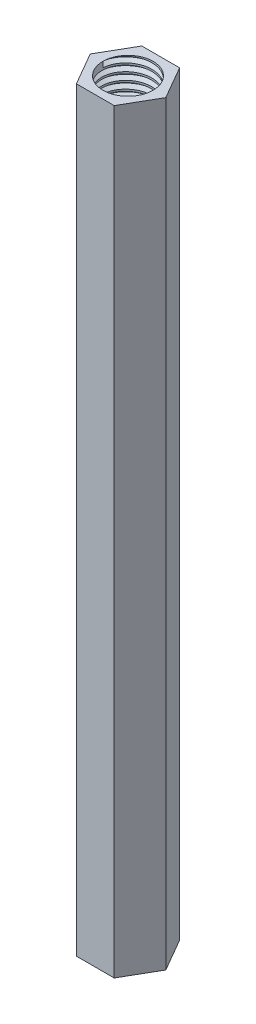
SolidWorks part; units mm, degrees
ref_plane "Front Plane" through (0, 0, 0) normal (0, 0, 1) x (1, 0, 0)
ref_plane "Top Plane" through (0, 0, 0) normal (0, 1, 0) x (1, 0, 0)
ref_plane "Right Plane" through (0, 0, 0) normal (1, 0, 0) x (0, 0, -1)
sketch "Sketch1" plane through (0, 0, 0) normal (0, 1, 0) x (1, 0, 0)
  line L1 (2.5, 0) -> (1.25, 2.1651)
  line L2 (1.25, 2.1651) -> (-1.25, 2.1651)
  line L3 (-1.25, 2.1651) -> (-2.5, 0)
  line L4 (-2.5, 0) -> (-1.25, -2.1651)
  line L5 (-1.25, -2.1651) -> (1.25, -2.1651)
  line L6 (1.25, -2.1651) -> (2.5, 0)
  circle A0 centre (0, 0) radius 2.1651 construction
  dimension "D1" = 2.5
extrude "Boss-Extrude1" add sketch "Sketch1" along normal blind 50
sketch "Sketch2" plane through (0, 50, 0) normal (0, 1, 0) x (1, 0, 0)
  circle A0 centre (0, 0) radius 1.6604
extrude "Cut-Extrude1" cut sketch "Sketch2" against normal through all
thread "Thread1" pitch 0.5 method cut profile "Thread Profile1" start angle 0, offset 0, length 10, pitch 0.5, diameter 3.3208
ref_plane "Plane1" through (1.6604, 0, 0) normal (0, 0, 1) x (1, 0, 0)
sketch "Thread Profile1" plane through (1.6604, 0, 0) normal (0, 0, 1) x (1, 0, 0)
  line L0 (0, 0) -> (0, 0.5) construction
  line L1 (0, 0) -> (0.2706, 0.1562)
  line L2 (0.2706, 0.1562) -> (0.2706, 0.2187)
  line L3 (0.2706, 0.2187) -> (0, 0.375)
  line L4 (0.2706, 0.1875) -> (0, 0.1875) construction
  line L11 (0, 0) -> (0, 0.375)
  point P2 (0, 0)
  dimension "Pitch" = 0.5
  dimension "Profile_Angle" = 60
  dimension "Profile_Land" = 0.0625
  dimension "Profile_Height" = 0.2706
thread "Thread2" pitch 0.5 method cut profile "Thread Profile2" start angle 0, offset 0, length 10, pitch 0.5, diameter 3.3208
ref_plane "Plane2" through (-1.6604, 50, 0) normal (0, 0, 1) x (-1, 0, 0)
sketch "Thread Profile2" plane through (-1.6604, 50, 0) normal (0, 0, 1) x (-1, 0, 0)
  line L0 (0, 0) -> (0, 0.5) construction
  line L1 (0, 0) -> (0.2706, 0.1562)
  line L2 (0.2706, 0.1562) -> (0.2706, 0.2187)
  line L3 (0.2706, 0.2187) -> (0, 0.375)
  line L4 (0.2706, 0.1875) -> (0, 0.1875) construction
  line L11 (0, 0) -> (0, 0.375)
  point P2 (0, 0)
  dimension "Pitch" = 0.5
  dimension "Profile_Angle" = 60
  dimension "Profile_Land" = 0.0625
  dimension "Profile_Height" = 0.2706
